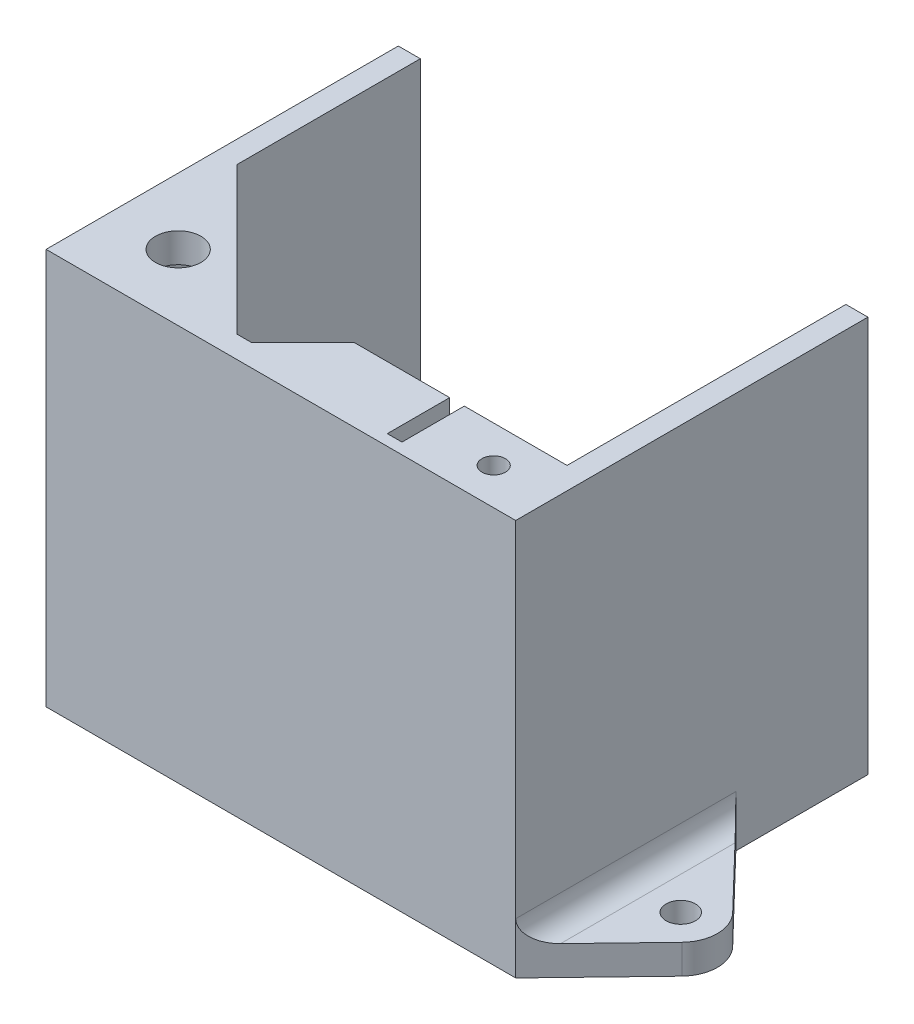
SolidWorks part; units mm, degrees
ref_plane "Płaszczyzna przednia" through (0, 0, 0) normal (0, 0, 1) x (1, 0, 0)
ref_plane "Płaszczyzna górna" through (0, 0, 0) normal (0, 1, 0) x (1, 0, 0)
ref_plane "Płaszczyzna prawa" through (0, 0, 0) normal (1, 0, 0) x (0, 0, -1)
sketch "Sketch1" plane through (0, 0, 0) normal (0, 1, 0) x (1, 0, 0)
  line L1 (-32, 24) -> (32, 24)
  line L2 (-32, 24) -> (-32, -24)
  line L3 (-32, -24) -> (32, -24)
  line L4 (32, 24) -> (32, -24)
  line L5 (-32, 24) -> (32, -24) construction
  line L6 (-32, -24) -> (32, 24) construction
  point P0 (0, 0)
  dimension "D1" = 64
  dimension "D2" = 48
extrude "Boss-Extrude1" add sketch "Sketch1" along normal blind 4
sketch "Sketch2" plane through (0, 0, 0) normal (0, -1, 0) x (1, 0, 0)
  line L9 (-20.8246, -16) -> (-22.4123, -13.25)
  line L10 (-22.4123, -13.25) -> (-25.5877, -13.25)
  line L11 (-25.5877, -13.25) -> (-27.1754, -16)
  line L12 (-27.1754, -16) -> (-25.5877, -18.75)
  line L13 (-25.5877, -18.75) -> (-22.4123, -18.75)
  line L14 (-22.4123, -18.75) -> (-20.8246, -16)
  line L15 (-32, -24) -> (-32, 24) construction
  line L16 (32, -24) -> (-32, -24) construction
  circle A0 centre (-24, -16) radius 2.75 construction
  dimension "D1" = 8
  dimension "D2" = 8
extrude "Cut-Extrude1" cut sketch "Sketch2" against normal blind 2.4
sketch "Sketch4" plane through (0, 0, 0) normal (0, -1, 0) x (1, 0, 0)
  line L0 (-32, -24) -> (-32, 24) construction
  line L1 (9.1754, 10) -> (7.5877, 12.75)
  line L2 (7.5877, 12.75) -> (4.4123, 12.75)
  line L3 (4.4123, 12.75) -> (2.8246, 10)
  line L4 (2.8246, 10) -> (4.4123, 7.25)
  line L5 (4.4123, 7.25) -> (7.5877, 7.25)
  line L6 (7.5877, 7.25) -> (9.1754, 10)
  line L8 (32, -24) -> (-32, -24) construction
  circle A0 centre (6, 10) radius 2.75 construction
  dimension "D1" = 38
  dimension "D2" = 34
extrude "Cut-Extrude2" cut sketch "Sketch4" against normal blind 2.4
sketch "Sketch6" plane through (0, 4, 0) normal (0, 1, 0) x (1, 0, 0)
  line L0 (-29, 21) -> (-29, 24)
  line L1 (-32, 24) -> (32, 24)
  line L2 (-32, 24) -> (-32, -24)
  line L3 (-32, -24) -> (32, -24)
  line L4 (32, 24) -> (32, -24)
  line L5 (-29, 21) -> (29, 21)
  line L6 (-29, 21) -> (-29, -21)
  line L7 (-29, -21) -> (29, -21)
  line L8 (29, 21) -> (29, -21)
  line L9 (-29, 21) -> (29, -21) construction
  line L10 (-29, -21) -> (29, 21) construction
  line L11 (29, 21) -> (29, 24)
  point P6 (0, 0)
  line M1 (32, -24) -> (32, 24)
  line M2 (32, 24) -> (-32, 24)
  line M3 (-32, 24) -> (-32, -24)
  line M4 (-32, -24) -> (32, -24)
  dimension "D1" = 58
  dimension "D2" = 42
extrude "Boss-Extrude3" add sketch "Sketch6" along normal blind 50 contours L11 L8 L7 L6 L0 M2 M3 M4 M1 region at (-29.8, 4, 0)
sketch "Sketch9" plane through (0, 4, 0) normal (0, 1, 0) x (1, 0, 0)
  line L0 (1, -13) -> (-7, -21)
  line L3 (29, -13) -> (1, -13)
  line L5 (-29, -21) -> (29, -21) construction
  line L6 (-7, -21) -> (29, -21)
  line L7 (1, -13) -> (-7, -21)
  line L9 (29, -21) -> (29, -13)
  line M3 (29, -21) -> (29, 24)
  line M6 (-29, -21) -> (29, -21)
  dimension "D1" = 8
  dimension "D2" = 8
  dimension "D3" = 28
extrude "Boss-Extrude4" add sketch "Sketch9" along normal blind 50 contours L3 L0 M3 M6 region at (12.9167, 4, 17.1667)
sketch "Sketch10" plane through (0, 0, 13) normal (0, 0, -1) x (-1, 0, 0)
  line L0 (-29, 54) -> (-29, 4) construction
  line L1 (-27, 39) -> (-1, 39)
  line L2 (-27, 39) -> (-27, 13)
  line L3 (-27, 13) -> (-1, 13)
  line L4 (-1, 39) -> (-1, 13)
  line L5 (-27, 39) -> (-1, 13) construction
  line L6 (-27, 13) -> (-1, 39) construction
  line L7 (-14, 39) -> (-14, 54) construction
  line L9 (-29, 54) -> (-1, 54) construction
  line L15 (-14.9986, 39) -> (-13.0014, 39)
  line L16 (-14.9986, 39) -> (-14.9986, 54)
  line L17 (-14.9986, 54) -> (-13.0014, 54)
  line L18 (-13.0014, 39) -> (-13.0014, 54)
  line L19 (-14.9986, 39) -> (-13.0014, 54) construction
  line L20 (-14.9986, 54) -> (-13.0014, 39) construction
  point P0 (-14, 26)
  point P9 (-14, 46.5)
  line M4 (-1, 4) -> (-1, 54)
  line M5 (-1, 54) -> (-29, 54)
  dimension "D1" = 26
  dimension "D2" = 26
  dimension "D3" = 15
  dimension "D5" = 28
extrude "Cut-Extrude4" cut sketch "Sketch10" against normal blind 9.5 contours L2 L3 L1 M4 | L1 M5 region at (14, 26, 13) region at (14, 46.5, 13)
sketch "Sketch13" plane through (0, 54, 0) normal (0, 1, 0) x (1, 0, 0)
  line L1 (29, -13) -> (-7.9463, -13)
  line L2 (29, -13) -> (29, -14)
  line L3 (29, -14) -> (-7.9463, -14)
  line L4 (-7.9463, -13) -> (-7.9463, -14)
  dimension "D1" = 1
extrude "Cut-Extrude6" cut sketch "Sketch13" against normal blind 32
sketch "Sketch15" plane through (0, 54, 0) normal (0, 1, 0) x (1, 0, 0)
  line L0 (-29, -1) -> (-9, -21)
  line L5 (-29, 24) -> (-29, -21) construction
  line L6 (-29, -21) -> (-7, -21) construction
  line L7 (-29, 24) -> (-29, -21) construction
  line L8 (-29, -1) -> (-29, -21)
  line L9 (-29, -21) -> (-9, -21)
  line L10 (-32, 24) -> (-32, -24) construction
  line L11 (-32, -24) -> (32, -24) construction
  circle A0 centre (-23, -15) radius 3.1
  dimension "D3" = 9
  dimension "D1" = 20
  dimension "D2" = 20
  dimension "D4" = 9
extrude "Boss-Extrude5" add sketch "Sketch15" against normal blind 4
sketch "Sketch17" plane through (0, 54, 0) normal (0, 1, 0) x (1, 0, 0)
  line L0 (32, -24) -> (32, 24) construction
  line L7 (-32, -24) -> (32, -24) construction
  line L8 (24, -19) -> (24, -24) construction
  line L9 (24, -19) -> (32, -19) construction
  line L11 (24, -15.8246) -> (21.25, -17.4123)
  line L12 (21.25, -17.4123) -> (21.25, -20.5877)
  line L13 (21.25, -20.5877) -> (24, -22.1754)
  line L14 (24, -22.1754) -> (26.75, -20.5877)
  line L15 (26.75, -20.5877) -> (26.75, -17.4123)
  line L16 (26.75, -17.4123) -> (24, -15.8246)
  circle A0 centre (24, -19) radius 2.75 construction
  dimension "D1" = 8
  dimension "D2" = 5
extrude "Cut-Extrude7" cut sketch "Sketch17" against normal blind 7
sketch "Sketch18" plane through (0, 0, 14) normal (0, 0, -1) x (-1, 0, 0)
  line L0 (-14.9986, 54) -> (-29, 54) construction
  line L1 (-26.8, 49.5) -> (-21.2, 49.5)
  line L2 (-26.8, 49.5) -> (-26.8, 47)
  line L3 (-26.8, 47) -> (-21.2, 47)
  line L4 (-21.2, 49.5) -> (-21.2, 47)
  line L5 (-32, 54) -> (-32, 0) construction
  point P6 (-24, 49.5)
  dimension "D1" = 7
  dimension "D2" = 2.5
  dimension "D3" = 5.6
  dimension "D4" = 8
extrude "Cut-Extrude8" cut sketch "Sketch18" against normal blind 5
sketch "Sketch19" plane through (0, 54, 0) normal (0, 1, 0) x (1, 0, 0)
  line L0 (24, -22.1754) -> (24, -15.8246) construction
  line L5 (26.75, -17.4123) -> (24, -15.8246) construction
  line L6 (24, -15.8246) -> (26.75, -19) construction
  line L7 (26.75, -20.5877) -> (26.75, -17.4123) construction
  line L8 (26.75, -19) -> (21.25, -19) construction
  line L10 (20.7023, -15.4012) -> (27.2977, -15.4012)
  line L11 (20.7023, -15.4012) -> (20.7023, -22.5988)
  line L12 (20.7023, -22.5988) -> (27.2977, -22.5988)
  line L13 (27.2977, -15.4012) -> (27.2977, -22.5988)
  line L14 (20.7023, -15.4012) -> (27.2977, -22.5988) construction
  line L15 (20.7023, -22.5988) -> (27.2977, -15.4012) construction
  circle A0 centre (24, -19) radius 1.6
extrude "Boss-Extrude8" add sketch "Sketch19" against normal blind 4.5
fillet "Fillet1" radius 1.5 2 edges at (-29, 50, 11) (-19, 50, 21)
sketch "Sketch20" plane through (0, 0, 0) normal (0, -1, 0) x (1, 0, 0)
  line L0 (32, 24) -> (43.1021, 12.4677)
  line L1 (39.5, 9) -> (32, 9) construction
  line L2 (32, -6) -> (43.1021, 5.5323)
  line L3 (-32, -24) -> (-42.9789, -14.5912)
  line L4 (32, -6) -> (32, 24)
  line L6 (-32, 2) -> (-32, -24)
  line L8 (-39.5, -11) -> (-32, -11) construction
  line L9 (-32, 2) -> (-42.9789, -7.4088)
  line L10 (-20.8246, -16) -> (-22.4123, -13.25) construction
  line L11 (-22.4123, -18.75) -> (-20.8246, -16) construction
  line L12 (-25.5877, -18.75) -> (-22.4123, -18.75) construction
  line L13 (-27.1754, -16) -> (-25.5877, -18.75) construction
  line L14 (-25.5877, -13.25) -> (-27.1754, -16) construction
  line L15 (-22.4123, -13.25) -> (-25.5877, -13.25) construction
  line L16 (9.1754, 10) -> (7.5877, 12.75) construction
  line L17 (7.5877, 7.25) -> (9.1754, 10) construction
  line L18 (4.4123, 7.25) -> (7.5877, 7.25) construction
  line L19 (2.8246, 10) -> (4.4123, 7.25) construction
  line L20 (4.4123, 12.75) -> (2.8246, 10) construction
  line L21 (7.5877, 12.75) -> (4.4123, 12.75) construction
  line L22 (-22.4123, -13.25) -> (-25.5877, -13.25) construction
  line L23 (-20.8246, -16) -> (-22.4123, -13.25) construction
  line L24 (-22.4123, -13.25) -> (-25.5877, -13.25) construction
  line L25 (-20.8246, -16) -> (-22.4123, -13.25) construction
  line L26 (32, -24) -> (32, 24)
  line L27 (32, 24) -> (-32, 24)
  line L28 (-32, 24) -> (-32, -24)
  line L29 (-32, -24) -> (32, -24)
  line L30 (32, -6) -> (32, 24)
  line L32 (-32, 2) -> (-32, -24)
  line L36 (9.1754, 10) -> (7.5877, 12.75)
  line L37 (7.5877, 7.25) -> (9.1754, 10)
  line L38 (4.4123, 7.25) -> (7.5877, 7.25)
  line L39 (2.8246, 10) -> (4.4123, 7.25)
  line L40 (4.4123, 12.75) -> (2.8246, 10)
  line L41 (7.5877, 12.75) -> (4.4123, 12.75)
  line L42 (9.1754, 10) -> (7.5877, 12.75) construction
  line L43 (7.5877, 7.25) -> (9.1754, 10) construction
  line L44 (4.4123, 7.25) -> (7.5877, 7.25) construction
  line L45 (2.8246, 10) -> (4.4123, 7.25) construction
  line L46 (4.4123, 12.75) -> (2.8246, 10) construction
  line L47 (7.5877, 12.75) -> (4.4123, 12.75) construction
  line L48 (-20.8246, -16) -> (-22.4123, -13.25)
  line L49 (-22.4123, -18.75) -> (-20.8246, -16)
  line L50 (-25.5877, -18.75) -> (-22.4123, -18.75)
  line L51 (-27.1754, -16) -> (-25.5877, -18.75)
  line L52 (-25.5877, -13.25) -> (-27.1754, -16)
  line L53 (-22.4123, -13.25) -> (-25.5877, -13.25)
  line L54 (-20.8246, -16) -> (-22.4123, -13.25) construction
  line L55 (-22.4123, -18.75) -> (-20.8246, -16) construction
  line L56 (-25.5877, -18.75) -> (-22.4123, -18.75) construction
  line L57 (-27.1754, -16) -> (-25.5877, -18.75) construction
  line L58 (-25.5877, -13.25) -> (-27.1754, -16) construction
  line L59 (-22.4123, -13.25) -> (-25.5877, -13.25) construction
  circle A0 centre (39.5, 9) radius 2
  circle A1 centre (-39.5, -11) radius 2
  arc A2 (43.1021, 5.5323) -> (43.1021, 12.4677) centre (39.5, 9) ccw
  arc A3 (-42.5162, -7.0122) -> (-42.5162, -14.9878) centre (-39.5, -11) ccw
  dimension "D1" = 0
  dimension "D2" = 0
  dimension "D3" = 0
extrude "Boss-Extrude9" add sketch "Sketch20" against normal blind 4 contours L9 A3 L3 L23 A1 | L2 A2 L0 L4 A0 region at (36.4432, 0, 9) region at (-36.5396, 0, -11)
fillet "Fillet2" radius 3 2 edges at (-32, 4, -11) (32, 4, 9)
sketch "Sketch22" plane through (0, 2.4, 0) normal (0, -1, 0) x (1, 0, 0)
  line L0 (4.4123, 12.75) -> (7.5877, 7.25) construction
  line L1 (7.5877, 7.25) -> (7.5877, 12.75) construction
  line L2 (7.5877, 12.75) -> (4.4123, 7.25) construction
  line L3 (-25.5877, -18.75) -> (-22.4123, -13.25) construction
  line L4 (-22.4123, -13.25) -> (-22.4123, -18.75) construction
  line L5 (-25.5877, -13.25) -> (-22.4123, -18.75) construction
  circle A0 centre (-24, -16) radius 1.65
  circle A1 centre (6, 10) radius 1.65
  dimension "D1" = 3.3
  dimension "D2" = 3.3
extrude "Cut-Extrude9" cut sketch "Sketch22" against normal blind 2
